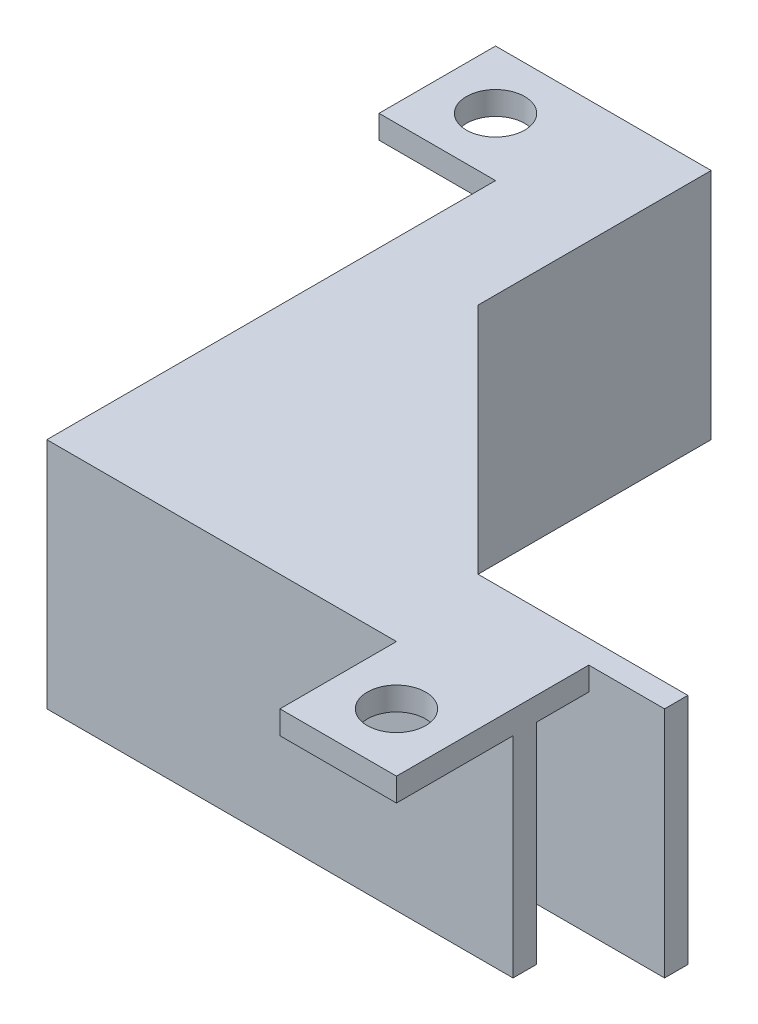
SolidWorks part; units mm, degrees
ref_plane "Front Plane" through (0, 0, 0) normal (0, 0, 1) x (1, 0, 0)
ref_plane "Top Plane" through (0, 0, 0) normal (0, 1, 0) x (1, 0, 0)
ref_plane "Right Plane" through (0, 0, 0) normal (1, 0, 0) x (0, 0, -1)
sketch "Sketch1" plane through (0, 0, 0) normal (0, 1, 0) x (1, 0, 0)
  line L1 (-20.5032, 25.038) -> (-18.5032, 25.038)
  line L2 (-20.5032, 25.038) -> (-20.5032, -14.962)
  line L3 (-20.5032, -14.962) -> (-18.5032, -14.962)
  line L4 (-18.5032, 25.038) -> (-18.5032, -14.962)
  line L5 (-18.5032, 25.038) -> (-14.0032, 25.038)
  line L6 (-18.5032, 25.038) -> (-18.5032, -14.962)
  line L7 (-18.5032, -14.962) -> (-14.0032, -14.962)
  line L8 (-14.0032, 25.038) -> (-14.0032, -14.962)
  line L9 (-14.0032, 25.038) -> (-12.0032, 25.038)
  line L10 (-14.0032, 25.038) -> (-14.0032, -14.962)
  line L11 (-14.0032, -14.962) -> (-12.0032, -14.962)
  line L12 (-12.0032, 25.038) -> (-12.0032, -14.962)
  line L13 (-14.0032, -14.962) -> (25.9968, -14.962)
  line L14 (-14.0032, -14.962) -> (-14.0032, -16.962)
  line L15 (-14.0032, -16.962) -> (25.9968, -16.962)
  line L16 (25.9968, -14.962) -> (25.9968, -16.962)
  line L17 (-14.0032, -16.962) -> (-20.5032, -16.962)
  line L18 (-14.0032, -16.962) -> (-14.0032, -14.962)
  line L19 (-14.0032, -14.962) -> (-20.5032, -14.962)
  line L20 (-20.5032, -16.962) -> (-20.5032, -14.962)
  line L21 (-20.5032, -16.962) -> (19.4968, -16.962)
  line L22 (-20.5032, -16.962) -> (-20.5032, -21.462)
  line L23 (-20.5032, -21.462) -> (19.4968, -21.462)
  line L24 (19.4968, -16.962) -> (19.4968, -21.462)
  line L25 (-20.5032, -21.462) -> (19.4968, -21.462)
  line L26 (-20.5032, -21.462) -> (-20.5032, -23.462)
  line L27 (-20.5032, -23.462) -> (19.4968, -23.462)
  line L28 (19.4968, -21.462) -> (19.4968, -23.462)
  line L29 (-18.5032, -14.962) -> (-20.5032, -14.962)
  line L30 (-18.5032, -14.962) -> (-18.5032, -23.462)
  line L31 (-18.5032, -23.462) -> (-20.5032, -23.462)
  line L32 (-20.5032, -14.962) -> (-20.5032, -23.462)
  dimension "D1" = 40
  dimension "D2" = 2
  dimension "D3" = 4.5
  dimension "D4" = 2
  dimension "D5" = 2
  dimension "D6" = 40
  dimension "D7" = 4.5
  dimension "D8" = 40
  dimension "D9" = 2
  dimension "D10" = 40
extrude "Walls" add sketch "Sketch1" against normal blind 20 contours L4 L1 L2 L3 | L12 L9 L8 L11 | L16 L13 L11 L14 L15 | L25 L30 L27 L28 | L30 L23 L26 L27 | L30 L21 L22 L23 | L30 L3 L20 L21 region at (-19.5032, 0, -5.038) region at (-19.5032, 0, 15.962) region at (-13.0032, 0, -5.038) region at (-19.5032, 0, 19.212) region at (5.9968, 0, 15.962) region at (-19.5032, 0, 22.462) region at (0.4968, 0, 22.462)
extrude "Rest on this" add sketch "Sketch1<3>" against normal blind 2 contours L8 L5 L4 L7 | L7 L30 L17 L14 | L17 L30 L25 L24 L15 region at (-16.2532, 0, -5.038) region at (-16.2532, 0, 15.962) region at (0.4968, 0, 19.212)
sketch "Sketch1<3>" plane through (0, 0, 0) normal (0, 1, 0) x (1, 0, 0) same geometry as "Sketch1"
sketch "Sketch2" plane through (0, 0, 0) normal (0, 1, 0) x (1, 0, 0)
  line L0 (7.9968, -14.962) -> (-12.0032, 5.038)
  line L5 (19.4968, -23.462) -> (9.4968, -23.462)
  line L6 (19.4968, -23.462) -> (19.4968, -33.462)
  line L7 (19.4968, -33.462) -> (9.4968, -33.462)
  line L8 (9.4968, -23.462) -> (9.4968, -33.462)
  line L9 (-20.5032, 25.038) -> (-30.5032, 25.038)
  line L10 (-20.5032, 25.038) -> (-20.5032, 15.038)
  line L11 (-20.5032, 15.038) -> (-30.5032, 15.038)
  line L12 (-30.5032, 25.038) -> (-30.5032, 15.038)
  line L13 (-12.0032, -14.962) -> (25.9968, -14.962) construction
  line L14 (-12.0032, 25.038) -> (-12.0032, -14.962) construction
  line L15 (14.4968, -23.462) -> (14.4968, -33.462) construction
  line L16 (9.4968, -28.462) -> (19.4968, -28.462) construction
  line L17 (-25.5032, 15.038) -> (-25.5032, 25.038) construction
  line L18 (-30.5032, 20.038) -> (-20.5032, 20.038) construction
  line L19 (7.9968, -14.962) -> (-12.0032, -14.962)
  line L20 (-12.0032, -14.962) -> (-12.0032, 5.038)
  circle A0 centre (14.4968, -28.462) radius 2.5
  circle A1 centre (-25.5032, 20.038) radius 2.5
  dimension "D5" = 5
  dimension "D6" = 5
  dimension "D1" = 20
  dimension "D2" = 10
  dimension "D3" = 10
  dimension "D4" = 20
extrude "Boss-Extrude3" add sketch "Sketch2" against normal blind 2
